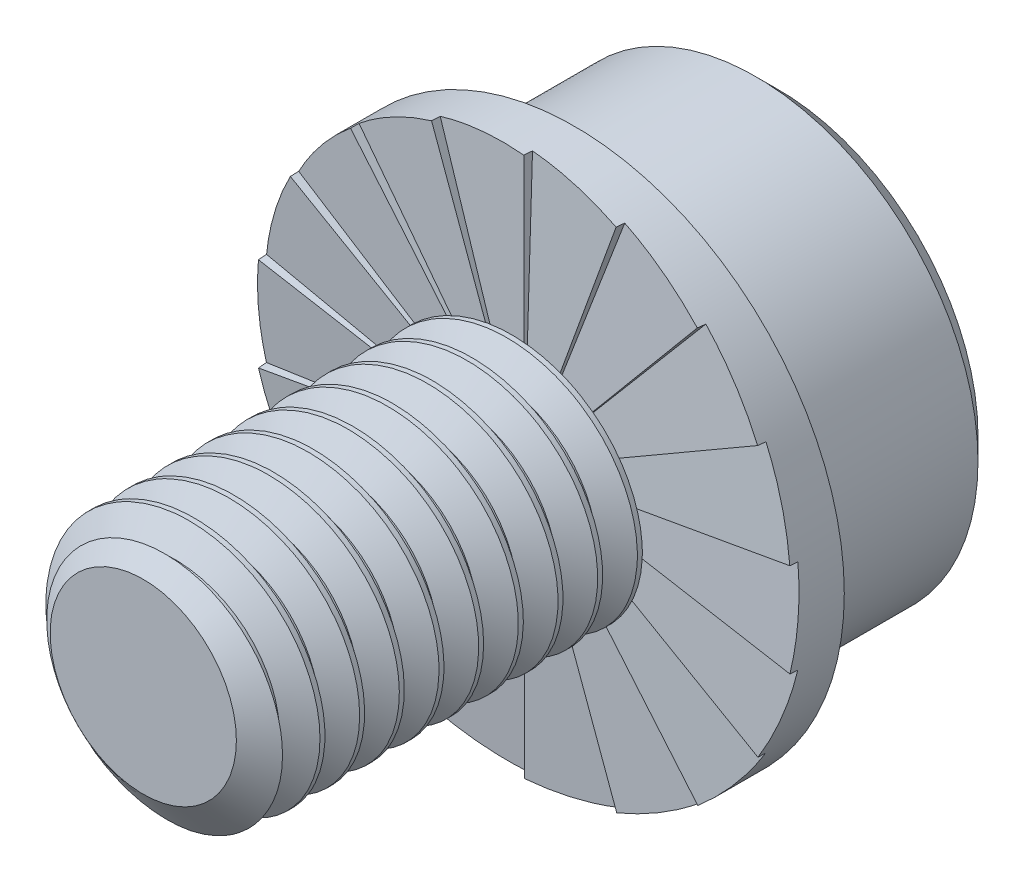
SolidWorks part; units mm, degrees
ref_plane "Front Plane" through (0, 0, 0) normal (0, 0, 1) x (1, 0, 0)
ref_plane "Top Plane" through (0, 0, 0) normal (0, 1, 0) x (1, 0, 0)
ref_plane "Right Plane" through (0, 0, 0) normal (1, 0, 0) x (0, 0, -1)
sketch "Sketch1" plane through (0, 0, 0) normal (0, 0, 1) x (1, 0, 0)
  circle A0 centre (0, 0) radius 4
  dimension "OD" = 8
extrude "Extrude1" add sketch "Sketch1" against normal blind 12
sketch "Sketch2" plane through (0, 0, 0) normal (0, 0, 1) x (1, 0, 0)
  circle A0 centre (0, 0) radius 4 construction
  circle A1 centre (0, 0) radius 4
curve "Helix/Spiral1" pitch 1.25 height 13.25 turns 10.6 parameters "pitch"=1.25
sketch "Sketch3" plane through (0, 0, 0) normal (1, 0, 0) x (0, 0, -1)
  line L0 (-1.0938, 4) -> (-0.625, 3.1881)
  line L1 (-0.625, 3.1881) -> (-0.4688, 3.1881)
  line L2 (-0.4688, 3.1881) -> (0, 4)
  line L3 (-1.0938, 4) -> (0, 4)
  line L4 (-0.5469, 4) -> (-0.5469, 3.1881) construction
  line L5 (-0.8594, 3.5941) -> (-0.2344, 3.5941) construction
  line L6 (0, 4) -> (0, -4) construction
  dimension "D1" = 0.1562
  dimension "D2" = 0.625
  dimension "D3" = 60
sweep "Cut-Sweep1" cut profiles "Sketch3" path "Helix/Spiral1"
sketch "Sketch4" plane through (0, 0, 0) normal (1, 0, 0) x (0, 0, -1)
  line L0 (0.7464, 4) -> (0, 2.9341)
  line L1 (0, 2.9341) -> (0, 4)
  line L2 (0.7464, 4) -> (0, 4)
  line L3 (-1.0938, 4) -> (0, 4) construction
  line L4 (0, 0) -> (7.0209, 0) construction
  dimension "D1" = 55
  dimension "D2" = 0.254
revolve "Cut-Revolve1" cut sketch "Sketch4" angle 360 about L4
sketch "Sketch5" plane through (0, 0, 0) normal (1, 0, 0) x (0, 0, -1)
  line L0 (12, -3.945) -> (12, 2.5877) construction
  line L1 (12, 4.127) -> (0.1202, 4.127)
  line L2 (12, 4.127) -> (12, 0)
  line L3 (12, 0) -> (0, 0)
  line L4 (0, 3.7968) -> (0, 0)
  line L5 (0.1202, 4.127) -> (0, 3.7968)
  line L6 (0, 0) -> (9.9695, 0) construction
  point P3 (0, 4.127)
  point P10 (0, 4.127)
  dimension "D1" = 0.3302
  dimension "Thread min" = 0
  dimension "D2" = 0.127
  dimension "D3" = 20
revolve "partially thread" [suppressed] add sketch "Sketch5" angle 360 about L6
sketch "Sketch6" plane through (0, 0, -12) normal (0, 0, -1) x (-1, 0, 0)
  circle A0 centre (0, 0) radius 7
  dimension "head dia" = 14
extrude "Extrude2" add sketch "Sketch6" along normal blind 8 separate body
sketch "Sketch10" plane through (0, 0, -12) normal (0, 0, 1) x (1, 0, 0)
  circle A0 centre (0, 0) radius 8.5
  dimension "Flange Diameter" = 17
extrude "Boss-Extrude1" add sketch "Sketch10" against normal blind 1.5875
sketch "Sketch18" plane through (0, 0, -12) normal (0, 0, 1) x (1, 0, 0)
  line L0 (0, 0) -> (0, 8.5) construction
  circle A0 centre (0, 0) radius 8.5 construction
  circle A1 centre (0, 0) radius 8.5 construction
ref_plane "Plane4" through (1.0419, 0, -11.9088) normal (0.0872, 0, -0.9962) x (-0.9962, 0, -0.0872)
sketch "Sketch19" plane through (1.0419, 0, -11.9088) normal (0.0872, 0, -0.9962) x (-0.9962, 0, -0.0872)
  line L0 (1.0459, 0) -> (1.0459, 11.04)
  line L1 (1.0459, 0) -> (4.8205, 10.3707)
  spline S0 degree 3 poles (0.3176, -11.04) (1.7742, -11.04) (2.4903, -10.9682) (3.5468, -10.7573) (3.8961, -10.6697) (4.5885, -10.4589) (4.9325, -10.3353) (5.933, -9.9188) (6.5656, -9.579) (7.4633, -8.977) (7.7551, -8.7599) (8.3157, -8.2978) (8.5824, -8.0546) (9.3434, -7.2902) (9.7986, -6.7341) (10.4014, -5.8286) (10.5883, -5.5153) (10.9271, -4.8784) (11.2332, -4.228) (11.4748, -3.551) (11.6837, -2.8605) (11.7722, -2.5065) (11.9835, -1.4396) (12.0532, -0.7244) (12.0537, 0.3541) (12.0364, 0.7146) (11.9658, 1.4376) (11.9126, 1.7974) (11.7026, 2.8577) (11.4954, 3.5451) (11.0831, 4.5468) (10.9276, 4.8775) (10.5875, 5.5168) (10.4029, 5.826) (9.8063, 6.7232) (9.3521, 7.281) (8.326, 8.3127) (7.769, 8.7711) (6.875, 9.3719) (6.5669, 9.5578) (5.9302, 9.9003) (5.6, 10.0574) (4.5986, 10.4743) (3.9117, 10.6837) (2.4998, 10.9671) (1.7692, 11.0397) (0.3303, 11.0403) (-0.3846, 10.9705) (-1.4503, 10.7585) (-1.8047, 10.6696) (-2.4954, 10.4594) (-3.1722, 10.2163) (-3.8216, 9.9086) (-4.4572, 9.5682) (-4.7695, 9.3806) (-5.6738, 8.7744) (-6.2284, 8.3171) (-6.9899, 7.5536) (-7.232, 7.2861) (-7.6918, 6.7244) (-7.9082, 6.4315) (-8.5076, 5.5314) (-8.8455, 4.8978) (-9.2594, 3.8971) (-9.3824, 3.5531) (-9.5922, 2.8598) (-9.6794, 2.5103) (-9.8895, 1.4533) (-9.9611, 0.7376) (-9.9625, -0.7168) (-9.8918, -1.4355) (-9.6836, -2.4922) (-9.5971, -2.8414) (-9.389, -3.5335) (-9.2666, -3.8781) (-8.8536, -4.8815) (-8.5165, -5.5157) (-7.7208, -6.7152) (-7.2568, -7.2842) (-6.2421, -8.305) (-5.6887, -8.7627) (-4.7883, -9.3689) (-4.4753, -9.5577) (-3.8389, -9.9001) (-3.5141, -10.0546) (-2.5202, -10.4694) (-1.8295, -10.6816) (-0.4032, -10.9682) (0.3176, -11.04) (1.7742, -11.04) (2.4903, -10.9682) knots -0.03125 -0.03125 0 0 0.03125 0.03125 0.046875 0.046875 0.0625 0.0625 0.09375 0.09375 0.109375 0.109375 0.125 0.125 0.15625 0.15625 0.171875 0.171875 0.1875 0.203125 0.203125 0.21875 0.21875 0.25 0.25 0.265625 0.265625 0.28125 0.28125 0.3125 0.3125 0.328125 0.328125 0.34375 0.34375 0.375 0.375 0.40625 0.40625 0.421875 0.421875 0.4375 0.4375 0.46875 0.46875 0.5 0.5 0.53125 0.53125 0.546875 0.546875 0.5625 0.578125 0.578125 0.59375 0.59375 0.625 0.625 0.640625 0.640625 0.65625 0.65625 0.6875 0.6875 0.703125 0.703125 0.71875 0.71875 0.75 0.75 0.78125 0.78125 0.796875 0.796875 0.8125 0.8125 0.84375 0.84375 0.875 0.875 0.90625 0.90625 0.921875 0.921875 0.9375 0.9375 0.96875 0.96875 1 1 1.03125 1.03125 1.046875 only from (1.0459, -11.04) to (1.0459, -11.04)
  spline S1 degree 3 poles (4.8205, 10.3707) (4.2939, 10.5636) (3.7556, 10.715) (2.4998, 10.9671) (1.7692, 11.0397) (1.0485, 11.04) (1.0472, 11.04) (1.0459, 11.04) knots 0.44441 0.44441 0.44441 0.44441 0.46875 0.46875 0.5 0.5 0.500057 0.500057 0.500057 0.500057
  dimension "D2" = 20
  dimension "D1" = 2.54
extrude "Cut-Extrude5" cut sketch "Sketch19" against normal blind 1.5875
pattern_circular "CirPattern1" count 18 over 360 about axis through (0, 0, 0) along (0, 0, 1) of "Cut-Extrude5"
sketch "Sketch20" plane through (0, 0, -12) normal (0, 0, -1) x (-1, 0, 0)
  arc A1 (0.5269, 3.1443) -> (-1.8622, 2.5877) centre (0, 0) ccw
  arc A2 (0.5269, 3.1443) -> (-1.8622, 2.5877) centre (0, 0) ccw
  arc A4 (-0.6611, -3.945) -> (2.3364, -3.2467) centre (0, 0) ccw
  arc A5 (-0.6611, -3.945) -> (2.3364, -3.2467) centre (0, 0) ccw
  spline S2 degree 3 poles (1044.9109, -1696.2285) (411.1075, -395.4017) (20.5247, 28.3281) (-2.9189, 1.6545) (-3.1043, 1.3542) (-3.3867, 0.6991) (-3.4756, 0.3584) (-3.5492, -0.3492) (-3.532, -0.7028) (-3.3217, -1.744) (-2.9645, -2.3895) (-2.2288, -3.1472) (-1.9448, -3.3687) (14.4806, -12.8879) (105.086, 91.6608) (-1477.3279, 1340.2354) knots -12.178841 -12.178841 -12.178841 -12.178841 0.125 0.125 0.25 0.25 0.375 0.375 0.5 0.5 0.75 0.75 0.875 0.875 7.50401 7.50401 7.50401 7.50401 only from (-1.8622, 2.5877) to (-0.6611, -3.945)
  spline S3 degree 3 poles (-1.8622, 2.5877) (-2.1736, 2.4128) (-2.4473, 2.191) (-2.9189, 1.6545) (-3.1043, 1.3542) (-3.3867, 0.6991) (-3.4756, 0.3584) (-3.5492, -0.3492) (-3.532, -0.7028) (-3.3217, -1.744) (-2.9645, -2.3895) (-2.2288, -3.1472) (-1.9448, -3.3687) (-1.3368, -3.721) (-1.0063, -3.8567) (-0.6611, -3.945) knots 0 0 0 0 0.125 0.125 0.25 0.25 0.375 0.375 0.5 0.5 0.75 0.75 0.875 0.875 1 1 1 1
  spline S4 degree 3 poles (-1597.6976, 1195.8169) (-303.5545, 170.1819) (-14.2778, -28.0967) (3.1366, -2.3098) (3.227, -2.1547) (3.3847, -1.8378) (3.452, -1.6753) (3.6176, -1.1748) (3.6807, -0.8186) (3.6964, -0.2901) (3.6889, -0.1141) (3.6484, 0.2374) (3.6148, 0.4141) (3.5236, 0.7561) (3.466, 0.9227) (3.3269, 1.2469) (3.2448, 1.4055) (2.9654, 1.8606) (2.739, 2.1297) (2.3325, 2.4766) (2.1875, 2.5813) (1.8859, 2.7642) (1.7282, 2.8433) (1.399, 2.9765) (1.2273, 3.0302) (-23.9003, 8.7068) (-106.5725, -276.0773) (-463.6832, -1941.7735) knots -10.812905 -10.812905 -10.812905 -10.812905 0.125 0.125 0.1875 0.1875 0.25 0.25 0.375 0.375 0.4375 0.4375 0.5 0.5 0.5625 0.5625 0.625 0.625 0.75 0.75 0.8125 0.8125 0.875 0.875 0.9375 0.9375 9.952184 9.952184 9.952184 9.952184 only from (2.3364, -3.2467) to (0.5269, 3.1443)
  spline S5 degree 3 poles (2.3364, -3.2467) (2.6064, -3.0131) (2.8398, -2.7493) (3.1366, -2.3098) (3.227, -2.1547) (3.3847, -1.8378) (3.452, -1.6753) (3.6176, -1.1748) (3.6807, -0.8186) (3.6964, -0.2901) (3.6889, -0.1141) (3.6484, 0.2374) (3.6148, 0.4141) (3.5236, 0.7561) (3.466, 0.9227) (3.3269, 1.2469) (3.2448, 1.4055) (2.9654, 1.8606) (2.739, 2.1297) (2.3325, 2.4766) (2.1875, 2.5813) (1.8859, 2.7642) (1.7282, 2.8433) (1.399, 2.9765) (1.2273, 3.0302) (0.8813, 3.1083) (0.7055, 3.1335) (0.5269, 3.1443) knots 0 0 0 0 0.125 0.125 0.1875 0.1875 0.25 0.25 0.375 0.375 0.4375 0.4375 0.5 0.5 0.5625 0.5625 0.625 0.625 0.75 0.75 0.8125 0.8125 0.875 0.875 0.9375 0.9375 1 1 1 1
  dimension "D1" = 0
extrude "Boss-Extrude2" add sketch "Sketch20" along normal up to next
sketch "Sketch7" plane through (0, 0, -20) normal (0, 0, -1) x (-1, 0, 0)
  line L1 (0, 3.4641) -> (-3, 1.7321)
  line L2 (-3, 1.7321) -> (-3, -1.7321)
  line L3 (-3, -1.7321) -> (0, -3.4641)
  line L4 (0, -3.4641) -> (3, -1.7321)
  line L5 (3, -1.7321) -> (3, 1.7321)
  line L6 (3, 1.7321) -> (0, 3.4641)
  circle A0 centre (0, 0) radius 3 construction
  dimension "hex dia" = 6
extrude "Cut-Extrude1" cut sketch "Sketch7" against normal blind 4.5
sketch "Sketch8" plane through (0, 0, -20) normal (0, 0, -1) x (-1, 0, 0)
  circle A0 centre (0, 0) radius 3.4641
extrude "Cut-Extrude2" cut sketch "Sketch8" against normal through all draft 45
chamfer "Chamfer1" distance 0.7 angle 45 1 edges at (-7, 0, -20)
sketch "Sketch9" plane through (0, 0, 0) normal (1, 0, 0) x (0, 0, -1)
  line L0 (0, 4) -> (0, -4) construction
  line L1 (6.875, 4) -> (6.875, -4) construction
  line L2 (0, -4) -> (6.875, -4) construction
  line L3 (0, 4) -> (6.875, 4) construction
  dimension "D1" = 6.875
fillet "Fillet1" radius 0.3969 1 edges at (7, 0, -13.5875)
equation "\"D3@Helix/Spiral1\" = \"screw length@Extrude1\"+\"pitch@Helix/Spiral1\""
equation "\"D1@Sketch3\" = \"pitch@Helix/Spiral1\"*.125"
equation "\"D2@Sketch3\" = \"pitch@Helix/Spiral1\"*.5"
equation "\"D1@Cut-Extrude1\" = \"hex dia@Sketch7\"*.75"
equation "\"D1@Chamfer1\" = \"head dia@Sketch6\"*.05"
equation "\"D1@Sketch9\" = \"pitch@Helix/Spiral1\"*5.5"
